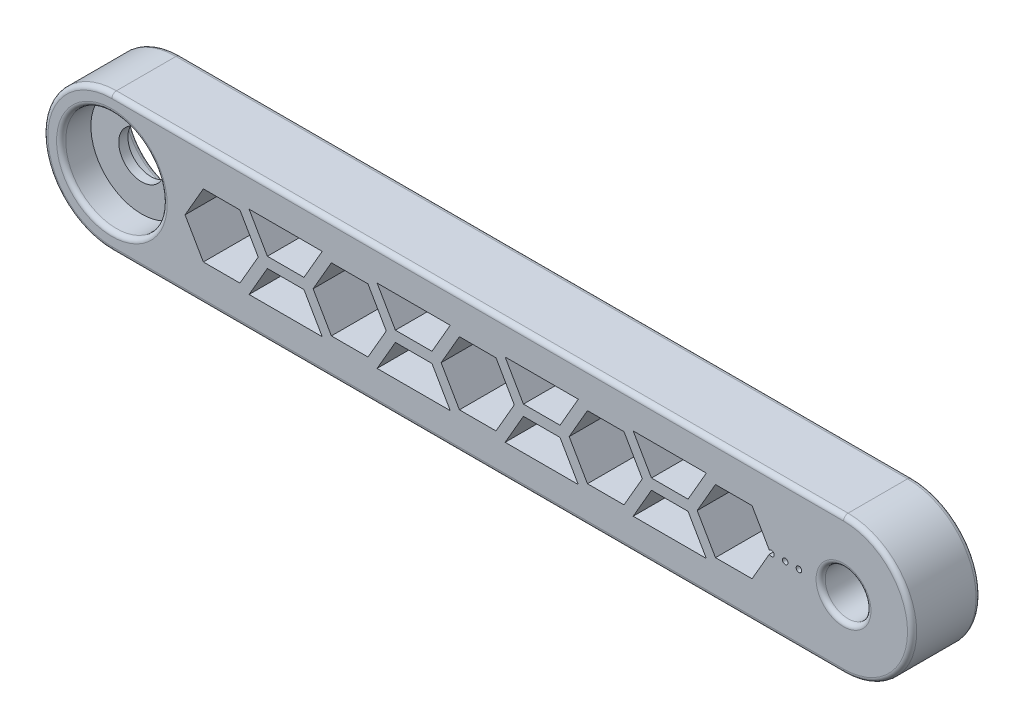
SolidWorks part; units mm, degrees
ref_plane "Front Plane" through (0, 0, 0) normal (0, 0, 1) x (1, 0, 0)
ref_plane "Top Plane" through (0, 0, 0) normal (0, 1, 0) x (1, 0, 0)
ref_plane "Right Plane" through (0, 0, 0) normal (1, 0, 0) x (0, 0, -1)
ref_axis "X" through (-88.99, 0, 0) along (1, 0, 0)
ref_axis "Y" through (0, 55, 0) along (0, -1, 0)
ref_axis "Z" through (0, 0, -88.99) along (0, 0, 1)
sketch "Sketch1" plane through (0, 0, 0) normal (0, 0, 1) x (1, 0, 0)
  line L0 (-80, 0) -> (80, 0) construction
  line L2 (-80, 15) -> (80, 15)
  line L3 (-80, -15) -> (80, -15)
  arc A0 (-80, 15) -> (-80, -15) centre (-80, 0) ccw
  arc A1 (80, -15) -> (80, 15) centre (80, 0) ccw
  circle A2 centre (80, 0) radius 11.1
  circle A3 centre (-80, 0) radius 11.1
  circle A4 centre (-80, 0) radius 5
  circle A5 centre (80, 0) radius 5
  point P5 (0, 0)
  dimension "D2" = 15
  dimension "D3" = 22.2
  dimension "D4" = 10
  dimension "D1" = 160
extrude "Boss-Extrude1" add sketch "Sketch1" along normal mid plane 2 contours L3 A1 L2 A0 A3 A2 | A4 A3 | A2 A5 region at (0, 0, 0) region at (69.214, 0, 0) region at (-90.786, 0, 0)
extrude "Boss-Extrude2" add sketch "Sketch1<3>" along normal mid plane 15 contours L3 A1 L2 A0 A3 A2 region at (0, 0, 0)
sketch "Sketch1<3>" plane through (0, 0, 0) normal (0, 0, 1) x (1, 0, 0) same geometry as "Sketch1"
sketch "Sketch2" plane through (0, 0, 0) normal (1, 0, 0) x (0, 0, -1)
  line L0 (-7.5, 15) -> (7.5, 15) construction
  line L1 (-7.5, 15) -> (7.5, 15)
  arc A0 (-3, 15) -> (3, 15) centre (0, 15) ccw
  point P6 (0, 15)
  dimension "D1" = 3
extrude "Cut-Extrude1" [suppressed] cut sketch "Sketch2" against normal through all both and the other way through all contours L1 A0
fillet "Fillet1" [suppressed] radius 1
mirror "Mirror3" [suppressed] about plane through (0, 0, 0) normal (0, 1, 0)
sketch "Sketch3" plane through (0, 0, 1) normal (0, 0, 1) x (1, 0, 0)
  circle A1 centre (80, 0) radius 11.1
  circle A2 centre (80, 0) radius 11.1
  circle A3 centre (80, 0) radius 5 construction
  circle A4 centre (80, 0) radius 5
  dimension "D1" = 0
extrude "Boss-Extrude3" add sketch "Sketch3" along normal up to surface (6.5 mm away) up to face at (91.1, 0, 7.5)
fillet "Fillet2" radius 1 12 edges at (-95, 0, 7.5) (0, 15, 7.5) (95, 0, 7.5) (0, -15, 7.5) (-68.9, 0, 7.5) (85, 0, 7.5) (95, 0, -7.5) (0, 15, -7.5) (-95, 0, -7.5) (0, -15, -7.5) (-68.9, 0, -7.5) (91.1, 0, -7.5)
mirror "Mirror1" [suppressed] about plane through (0, 0, 0) normal (1, 0, 0) of bodies 104
delete or keep bodies "Body-Delete/Keep 1" [suppressed] type keep bodies bodies 105
sketch "Sketch4" plane through (0, 0, 7.5) normal (0, 0, 1) x (1, 0, 0)
  circle A0 centre (70.25, 0) radius 0.75 construction
  circle A1 centre (67.25, 0) radius 0.75 construction
  circle A2 centre (64.25, 0) radius 0.75 construction
  circle A3 centre (61.25, 0) radius 0.75 construction
  circle A4 centre (70.25, 0) radius 0.75 construction
  circle A5 centre (67.25, 0) radius 0.75 construction
  circle A6 centre (64.25, 0) radius 0.75 construction
  circle A7 centre (61.25, 0) radius 0.75 construction
  circle A8 centre (61.25, 0) radius 0.6
  circle A9 centre (64.25, 0) radius 0.6
  circle A10 centre (67.25, 0) radius 0.6
  circle A11 centre (70.25, 0) radius 0.6
  dimension "D1" = 1.2
extrude "Cut-Extrude2" cut sketch "Sketch4" against normal offset from surface (6.5 mm away) 2 up to face at (-75, 0, -1)
sketch "Sketch5" plane through (0, 0, 0) normal (0, 0, 1) x (1, 0, 0)
  line L0 (6, 8.0829) -> (10, 1.1547)
  line L1 (4, -6.9282) -> (8, 0)
  line L2 (8, 0) -> (4, 6.9282)
  line L3 (4, 6.9282) -> (-4, 6.9282)
  line L4 (-4, 6.9282) -> (-8, 0)
  line L5 (-8, 0) -> (-4, -6.9282)
  line L6 (-4, -6.9282) -> (4, -6.9282)
  line L7 (10, 1.1547) -> (18, 1.1547)
  line L8 (18, 1.1547) -> (22, 8.0829)
  line L9 (22, 8.0829) -> (6, 8.0829)
  line L10 (6, 3.4641) -> (8, 4.6188) construction
  line L11 (0, 0) -> (8, 0) construction
  line L12 (10, -1.1547) -> (18, -1.1547)
  line L13 (18, -1.1547) -> (22, -8.0829)
  line L14 (22, -8.0829) -> (6, -8.0829)
  line L15 (6, -8.0829) -> (10, -1.1547)
  circle A0 centre (0, 0) radius 6.9282 construction
  dimension "D1" = 8
  dimension "D2" = 2
extrude "Cut-Extrude3" cut sketch "Sketch5" against normal through all both and the other way through all contours L5 L6 L1 L2 L3 L4 region at (0, 0, 0)
extrude "Cut-Extrude4" cut sketch "Sketch5<3>" against normal through all both and the other way through all contours L15 L14 L13 L12 | L8 L9 L0 L7 region at (14, 5.0037, 0) region at (14, -5.0037, 0)
sketch "Sketch5<3>" plane through (0, 0, 0) normal (0, 0, 1) x (1, 0, 0) same geometry as "Sketch5"
pattern_linear "LPattern1" count 3 spacing 28 along (1, 0, 0) count 3 spacing 28 along (-1, 0, 0) of "Cut-Extrude3"
pattern_linear "LPattern2" count 2 spacing 28 along (1, 0, 0) count 3 spacing 28 along (-1, 0, 0) of "Cut-Extrude4"
